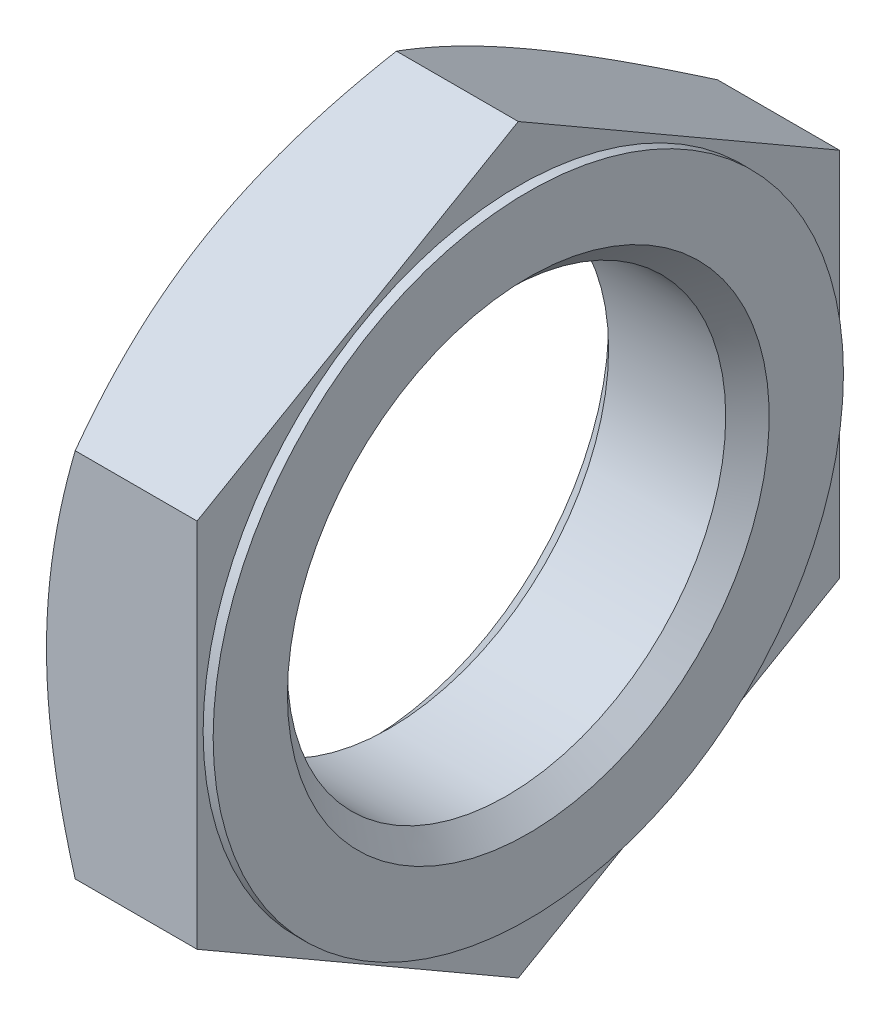
SolidWorks part; units mm, degrees
ref_plane "前视基准面" through (0, 0, 0) normal (0, 0, 1) x (1, 0, 0)
ref_plane "上视基准面" through (0, 0, 0) normal (0, 1, 0) x (1, 0, 0)
ref_plane "右视基准面" through (0, 0, 0) normal (1, 0, 0) x (0, 0, -1)
sketch "草图1" plane through (0, 0, 0) normal (0, 0, 1) x (1, 0, 0)
  line L0 (0, 0) -> (0, 16)
  line L1 (0, 16) -> (1.4434, 18.5)
  line L2 (1.4434, 18.5) -> (7.5, 18.5)
  line L3 (7.5, 18.5) -> (7.5, 15.7)
  line L4 (7.5, 15.7) -> (8, 15.7)
  line L5 (8, 15.7) -> (8, 0)
  line L6 (8, 0) -> (0, 0)
  line L7 (8, 0) -> (0, 0) construction
revolve "旋转1" add sketch "草图1" angle 360 about L7 reverse direction yes
sketch "草图2" plane through (0, 0, 0) normal (0, 0, 1) x (1, 0, 0)
  line L0 (0, 0) -> (0, 12)
  line L1 (0, 12) -> (1.0825, 10.9175)
  line L2 (1.0825, 10.9175) -> (6.9175, 10.9175)
  line L3 (6.9175, 10.9175) -> (8, 12)
  line L4 (8, 12) -> (8, 0)
  line L5 (8, 0) -> (0, 0)
  line L6 (8, 0) -> (0, 0) construction
revolve "切除-旋转1" cut sketch "草图2" angle 360 about L6 reverse direction yes
cosmetic thread "装饰螺纹线1" parameters "D1"=8, "D2"=24
sketch "草图3" plane through (0, 0, 0) normal (1, 0, 0) x (0, 0, -1)
  line L0 (-32, 32) -> (-32, -32)
  line L1 (-32, -32) -> (32, -32)
  line L2 (32, -32) -> (32, 32)
  line L3 (32, 32) -> (-32, 32)
  line L4 (-16, -9.2376) -> (0, -18.4752)
  line L5 (0, -18.4752) -> (16, -9.2376)
  line L6 (16, -9.2376) -> (16, 9.2376)
  line L7 (16, 9.2376) -> (0, 18.4752)
  line L8 (0, 18.4752) -> (-16, 9.2376)
  line L9 (-16, 9.2376) -> (-16, -9.2376)
extrude "切除-拉伸1" cut sketch "草图3" along normal blind 8
ref_plane "基准面4" through (4, 0, 0) normal (1, 0, 0) x (0, 0, -1)
ref_plane "基准面5" through (8, 0, 0) normal (1, 0, 0) x (0, 0, -1)
ref_plane "nut XY" through (4, 0, 0) normal (-1, 0, 0) x (0, 0, 1)
ref_plane "nut XZ" through (0, 0, 0) normal (0, 1, 0) x (1, 0, 0)
ref_plane "nut YZ" through (0, 0, 0) normal (0, 0, -1) x (-1, 0, 0)
ref_axis "nut X" through (4, 0, 80.9) along (0, 0, -1)
ref_axis "nut Y" through (4, 50, 0) along (0, -1, 0)
ref_axis "nut Z" through (-80.9, 0, 0) along (1, 0, 0)
sketch3d "nut"
  point P0 (4, 0, 0)
ref_plane "nut1 XY" through (8, 0, 0) normal (-1, 0, 0) x (0, 0, 1)
ref_plane "nut1 XZ" through (0, 0, 0) normal (0, 1, 0) x (1, 0, 0)
ref_plane "nut1 YZ" through (0, 0, 0) normal (0, 0, -1) x (-1, 0, 0)
ref_axis "nut1 X" through (8, 0, 80.9) along (0, 0, -1)
ref_axis "nut1 Y" through (8, 50, 0) along (0, -1, 0)
ref_axis "nut1 Z" through (-80.9, 0, 0) along (1, 0, 0)
sketch3d "nut1"
  point P0 (8, 0, 0)
